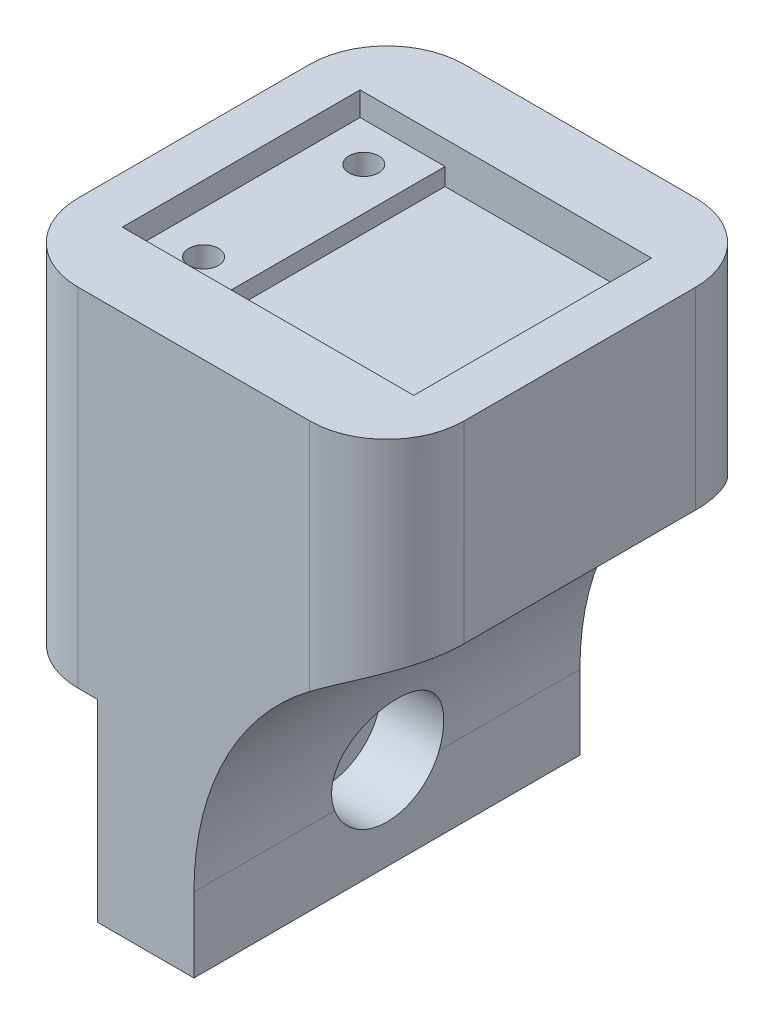
SolidWorks part; units mm, degrees
ref_plane "Front Plane" through (0, 0, 0) normal (0, 0, 1) x (1, 0, 0)
ref_plane "Top Plane" through (0, 0, 0) normal (0, 1, 0) x (1, 0, 0)
ref_plane "Right Plane" through (0, 0, 0) normal (1, 0, 0) x (0, 0, -1)
sketch "Profile" plane through (0, 0, 0) normal (0, 0, 1) x (1, 0, 0)
  line L1 (-6.35, 22.86) -> (6.35, 22.86)
  line L2 (-6.35, 22.86) -> (-6.35, 0)
  line L3 (-6.35, 0) -> (6.35, 0)
  line L4 (6.35, 22.86) -> (6.35, 0)
  line L5 (0, 0) -> (6.35, 0)
  line L6 (0, 0) -> (0, -12.7)
  line L7 (0, -12.7) -> (6.35, -12.7)
  line L8 (6.35, 0) -> (6.35, -12.7)
  dimension "D1" = 22.86
  dimension "D2" = 12.7
  dimension "D3" = 6.35
  dimension "D4" = 12.7
extrude "Boss-Extrude1" add sketch "Profile" along normal mid plane 25.4 contours L4 L1 L2 L3 | L8 L3 L6 L7 region at (0, 11.43, 0) region at (3.175, -6.35, 0)
sketch "ScrewHole" plane through (0, 0, 0) normal (-1, 0, 0) x (0, 0, 1)
  line L1 (12.7, -12.7) -> (-12.7, -12.7) construction
  line L2 (12.7, 0) -> (-12.7, 0) construction
  circle A0 centre (0, -6.477) radius 2.159
  point P10 (0, -12.7)
  dimension "D1" = 4.318
  dimension "D2" = 6.477
extrude "Cut-Extrude1" cut sketch "ScrewHole" against normal through all both
sketch "Sketch3" plane through (6.35, 0, 0) normal (1, 0, 0) x (0, 0, -1)
  circle A0 centre (0, -6.477) radius 2.159 construction
  circle A1 centre (0, -6.477) radius 2.159
  circle A2 centre (0, -6.477) radius 3.683
  dimension "D1" = 7.366
extrude "Cut-Extrude2" cut sketch "Sketch3" against normal blind 4.064
sketch "Sketch4" plane through (6.35, 0, 0) normal (1, 0, 0) x (0, 0, -1)
  line L0 (12.7, 22.86) -> (12.7, -12.7) construction
  line L1 (-12.7, 22.86) -> (12.7, 22.86)
  line L2 (-12.7, 22.86) -> (-12.7, 10.16)
  line L3 (-12.7, 10.16) -> (12.7, 10.16)
  line L4 (12.7, 22.86) -> (12.7, 10.16)
  dimension "D1" = 12.7
extrude "Boss-Extrude2" add sketch "Sketch4" along normal blind 12.7
sketch "Sketch6" plane through (0, 22.86, 0) normal (0, 1, 0) x (1, 0, 0)
  line L0 (-6.35, -12.7) -> (-6.35, 12.7) construction
  line L1 (-3.2385, 7.8232) -> (15.9385, 7.8232)
  line L2 (-3.2385, 7.8232) -> (-3.2385, -7.8232)
  line L3 (-3.2385, -7.8232) -> (15.9385, -7.8232)
  line L4 (15.9385, 7.8232) -> (15.9385, -7.8232)
  line L5 (-6.35, -12.7) -> (19.05, -12.7) construction
  point P6 (-6.35, 0)
  point P7 (-3.2385, 0)
  point P10 (6.35, -12.7)
  point P11 (6.35, -7.8232)
  dimension "D1" = 19.177
  dimension "D2" = 15.6464
extrude "Cut-Extrude3" cut sketch "Sketch6" against normal blind 1.5748
sketch "Sketch7" plane through (0, 21.2852, 0) normal (0, 1, 0) x (1, 0, 0)
  line L0 (13.1445, 5.2705) -> (13.1445, -5.2705) construction
  line L1 (15.9385, -7.8232) -> (15.9385, 7.8232) construction
  line L2 (6.35, 7.8232) -> (6.35, -7.8232) construction
  line L3 (15.9385, 7.8232) -> (-3.2385, 7.8232) construction
  line L4 (-3.2385, -7.8232) -> (15.9385, -7.8232) construction
  circle A0 centre (13.1445, 5.2705) radius 0.9779
  circle A1 centre (13.1445, -5.2705) radius 0.9779
  circle A2 centre (-0.4445, -5.2705) radius 0.9779
  circle A3 centre (-0.4445, 5.2705) radius 0.9779
  point P6 (15.9385, 0)
  point P7 (13.1445, 0)
  dimension "D3" = 1.9558
  dimension "D4" = 1.9558
  dimension "D1" = 10.541
  dimension "D2" = 2.794
ref_plane "Plane1" through (6.35, 0, 0) normal (1, 0, 0) x (0, 0, -1)
sketch "Sketch9" plane through (0, 21.2852, 0) normal (0, 1, 0) x (1, 0, 0)
  line L0 (-3.2385, -7.8232) -> (15.9385, -7.8232) construction
  line L1 (2.3495, 7.8232) -> (15.9385, 7.8232)
  line L2 (2.3495, 7.8232) -> (2.3495, -7.8232)
  line L3 (2.3495, -7.8232) -> (15.9385, -7.8232)
  line L4 (15.9385, 7.8232) -> (15.9385, -7.8232)
  line L7 (15.9385, -7.8232) -> (15.9385, 7.8232) construction
  line L8 (-3.2385, 7.8232) -> (-3.2385, -7.8232) construction
  line L9 (15.9385, 7.8232) -> (-3.2385, 7.8232) construction
  dimension "D1" = 5.588
extrude "Cut-Extrude5" cut sketch "Sketch9" against normal blind 1.143
extrude "Cut-Extrude6" cut sketch "Sketch7" against normal blind 12.7 contours A2 | A3
fillet "Fillet1" radius 19.05 1 edges at (6.35, 10.16, 0)
fillet "Fillet2" radius 5.08 4 edges at (-6.35, 11.43, -12.7) (19.05, 16.51, -12.7) (-6.35, 11.43, 12.7) (19.05, 16.51, 12.7)
